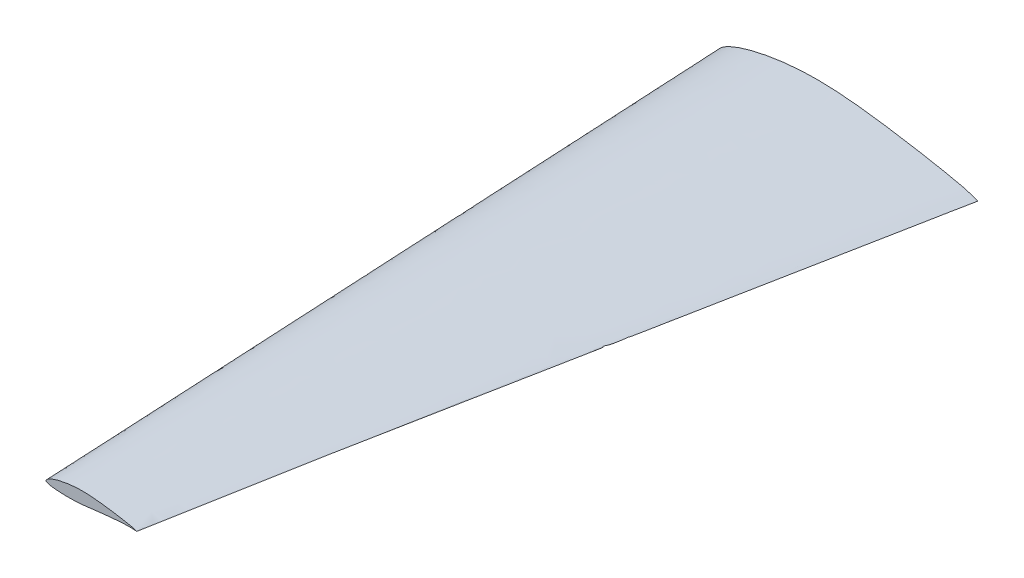
SolidWorks part; units mm, degrees
ref_plane "Front Plane" through (0, 0, 0) normal (0, 0, 1) x (1, 0, 0)
ref_plane "Top Plane" through (0, 0, 0) normal (0, 1, 0) x (1, 0, 0)
ref_plane "Right Plane" through (0, 0, 0) normal (1, 0, 0) x (0, 0, -1)
curve "Curve1"
  spline degree 3 poles (0.9921, 0.0008, 0) (1.0019, -0.0008, 0) (0.9929, 0.0016, 0) (0.9861, 0.0043, 0) (0.9706, 0.0096, 0) (0.9519, 0.0152, 0) (0.9278, 0.021, 0) (0.8992, 0.0273, 0) (0.8662, 0.0341, 0) (0.8293, 0.0413, 0) (0.789, 0.0488, 0) (0.746, 0.0564, 0) (0.7007, 0.0641, 0) (0.6538, 0.0714, 0) (0.6058, 0.0784, 0) (0.5573, 0.0846, 0) (0.5088, 0.0898, 0) (0.4609, 0.0938, 0) (0.4138, 0.0961, 0) (0.3679, 0.0966, 0) (0.3232, 0.0952, 0) (0.2801, 0.092, 0) (0.2388, 0.0874, 0) (0.1997, 0.0815, 0) (0.1631, 0.0746, 0) (0.1296, 0.0669, 0) (0.0993, 0.0585, 0) (0.0726, 0.0496, 0) (0.0499, 0.0404, 0) (0.0312, 0.031, 0) (0.0168, 0.0217, 0) (0.0085, 0.0145, 0) (0.0039, 0.009, 0) (0.0018, 0.0058, 0) (0.0004, 0.0024, 0) (0, 0.0003, 0) (0, -0.0012, 0) (0.0006, -0.0026, 0) (0.002, -0.0043, 0) (0.0049, -0.007, 0) (0.0107, -0.0108, 0) (0.0215, -0.0156, 0) (0.0378, -0.0206, 0) (0.0598, -0.0253, 0) (0.0864, -0.0294, 0) (0.1174, -0.033, 0) (0.1523, -0.036, 0) (0.1908, -0.0383, 0) (0.2323, -0.0397, 0) (0.2764, -0.0402, 0) (0.3228, -0.0395, 0) (0.3711, -0.0373, 0) (0.4212, -0.0335, 0) (0.4729, -0.0284, 0) (0.526, -0.0227, 0) (0.5798, -0.0169, 0) (0.6336, -0.0114, 0) (0.6866, -0.0064, 0) (0.7378, -0.0023, 0) (0.7866, 0.0009, 0) (0.832, 0.0031, 0) (0.8733, 0.0042, 0) (0.9096, 0.0045, 0) (0.9406, 0.0038, 0) (0.9645, 0.0029, 0) (0.984, 0.0013, 0) (0.9921, 0.0008, 0) (1.0019, -0.0008, 0) (0.9929, 0.0016, 0) knots -0.016161 -0.007282 -0.001839 0 0.00178 0.006777 0.014308 0.024046 0.036116 0.050547 0.06713 0.085624 0.105767 0.127282 0.149864 0.17323 0.197069 0.221103 0.245052 0.268663 0.291773 0.314299 0.336178 0.357377 0.377792 0.397225 0.415489 0.432417 0.447849 0.461651 0.473687 0.483898 0.492263 0.498797 0.499955 0.502811 0.504371 0.50536 0.505925 0.506503 0.507535 0.509205 0.512345 0.517665 0.526422 0.537425 0.550643 0.565966 0.583206 0.602155 0.622587 0.644255 0.666998 0.690703 0.715307 0.740824 0.767084 0.793717 0.820331 0.846519 0.871863 0.895937 0.918335 0.938667 0.956573 0.971715 0.983839 0.992718 0.998161 1 1.00178 1.006777 1.014308 periodic
sketch "Sketch1" plane through (0, 0, 0) normal (0, 0, 1) x (1, 0, 0)
  line L0 (1122.2059, -30.8288) -> (-1162.7941, -35.0845) construction
  spline S1 degree 3 poles (1104.1363, -28.0222) (1126.6295, -31.7875) (1105.8826, -26.3024) (1090.4575, -20.1288) (1054.9513, -7.9956) (1012.296, 4.6638) (957.0478, 17.8508) (891.7164, 32.0367) (816.2153, 47.3864) (731.9108, 63.6705) (639.9041, 80.612) (541.5101, 97.9168) (438.0076, 115.0958) (330.7593, 131.7488) (221.0675, 147.3336) (110.2357, 161.251) (-0.493, 172.9975) (-110.0556, 181.8587) (-217.6516, 186.9061) (-322.6724, 187.859) (-424.6755, 184.4831) (-523.1626, 176.9995) (-617.5035, 166.1709) (-706.8843, 152.6667) (-790.3524, 136.737) (-867.0563, 118.889) (-936.2082, 99.5088) (-997.0691, 79.0242) (-1049.0447, 57.9028) (-1091.6336, 36.4479) (-1124.4686, 15.1943) (-1143.3869, -1.4067) (-1153.8659, -14.0298) (-1158.6984, -21.3016) (-1161.9612, -29.0988) (-1162.8988, -33.8887) (-1162.7223, -37.2464) (-1161.3764, -40.4052) (-1158.2301, -44.4654) (-1151.5185, -50.6376) (-1138.2079, -59.2164) (-1113.635, -70.0567) (-1076.2399, -81.3981) (-1026.0446, -92.1031) (-965.2298, -101.4019) (-894.4776, -109.4657) (-814.6314, -116.0953) (-726.7099, -121.1028) (-631.8133, -124.2931) (-530.9633, -125.2112) (-425.0342, -123.2363) (-314.6436, -117.9744) (-200.1569, -109.1265) (-81.9663, -97.1903) (39.2548, -83.9633) (162.1641, -70.4688) (285.0306, -57.6215) (406.0083, -46.0046) (523.1884, -36.2734) (634.6311, -28.7415) (738.3789, -23.5277) (832.7109, -20.7776) (915.5317, -20.0924) (986.36, -21.3847) (1040.9806, -23.338) (1085.6437, -26.9173) (1104.1363, -28.0222) (1126.6295, -31.7875) (1105.8826, -26.3024) knots -0.016161 -0.007282 -0.001839 0 0.00178 0.006777 0.014308 0.024046 0.036116 0.050547 0.06713 0.085624 0.105767 0.127282 0.149864 0.17323 0.197069 0.221103 0.245052 0.268663 0.291773 0.314299 0.336178 0.357377 0.377792 0.397225 0.415489 0.432417 0.447849 0.461651 0.473687 0.483898 0.492263 0.498797 0.499955 0.502811 0.504371 0.50536 0.505925 0.506503 0.507535 0.509205 0.512345 0.517665 0.526422 0.537425 0.550643 0.565966 0.583206 0.602155 0.622587 0.644255 0.666998 0.690703 0.715307 0.740824 0.767084 0.793717 0.820331 0.846519 0.871863 0.895937 0.918335 0.938667 0.956573 0.971715 0.983839 0.992718 0.998161 1 1.00178 1.006777 1.014308 only from (1122.2059, -30.8288) to (1122.2059, -30.8288)
  dimension "D1" = 2285
ref_plane "Plane1" through (0, 0, 6200) normal (0, 0, 1) x (1, 0, 0)
ref_plane "Plane3" through (0, -35.0845, 0) normal (0, 1, 0) x (1, 0, 0)
sketch "Sketch4" plane through (0, -35.0845, 0) normal (0, 1, 0) x (1, 0, 0)
  line L1 (1122.2059, 0) -> (-1162.7941, 0) construction
  line L2 (-172.1886, -6200) -> (172.1886, -6200) construction
  line L4 (-1162.7941, 0) -> (-862.7941, -6200)
sketch "Sketch5" plane through (0, 0, 6200) normal (0, 0, 1) x (1, 0, 0)
  line L0 (-62.749, -35.2354) -> (-862.7688, -35.3009) construction
  spline S1 degree 3 poles (-69.0897, -34.3504) (-61.22, -35.5469) (-68.4893, -33.741) (-73.9048, -31.6671) (-86.3598, -27.6181) (-101.3126, -23.4229) (-120.663, -19.1093) (-143.5377, -14.4998) (-169.9677, -9.5373) (-199.4749, -4.2947) (-231.6736, 1.1372) (-266.1033, 6.6624) (-302.3153, 12.1171) (-339.8318, 17.3686) (-378.1955, 22.2345) (-416.9483, 26.5125) (-455.6538, 30.0335) (-493.9373, 32.5536) (-531.5145, 33.7529) (-568.1715, 33.5367) (-603.7528, 31.8256) (-638.0855, 28.6992) (-670.9538, 24.4271) (-702.0769, 19.2472) (-731.124, 13.2516) (-757.8002, 6.6219) (-781.8329, -0.5031) (-802.9662, -7.9701) (-820.9952, -15.6131) (-835.7466, -23.3233) (-847.0949, -30.9123) (-853.6106, -36.8049) (-857.2018, -41.2651) (-858.8503, -43.8282) (-859.9483, -46.5664) (-860.2505, -48.243) (-860.1714, -49.4139) (-859.6851, -50.5093) (-858.5659, -51.9099) (-856.1913, -54.0289) (-851.5011, -56.9533) (-842.8685, -60.6082) (-829.7584, -64.3709) (-812.1844, -67.8447) (-790.9116, -70.7722) (-766.1771, -73.2167) (-738.2762, -75.1133) (-707.5656, -76.4015) (-674.4302, -77.0191) (-639.2289, -76.8125) (-602.2702, -75.5698) (-563.7715, -73.1566) (-523.8621, -69.4706) (-482.6761, -64.6873) (-440.4393, -59.4377) (-397.6147, -54.086) (-354.8016, -48.9603) (-312.6413, -44.2739) (-271.7964, -40.2655) (-232.9425, -37.0546) (-196.7619, -34.6929) (-163.8546, -33.2402) (-134.9538, -32.5684) (-110.2281, -32.6493) (-91.1554, -33.0456) (-75.5494, -34.0614) (-69.0897, -34.3504) (-61.22, -35.5469) (-68.4893, -33.741) knots -0.016161 -0.007282 -0.001839 0 0.00178 0.006777 0.014308 0.024046 0.036116 0.050547 0.06713 0.085624 0.105767 0.127282 0.149864 0.17323 0.197069 0.221103 0.245052 0.268663 0.291773 0.314299 0.336178 0.357377 0.377792 0.397225 0.415489 0.432417 0.447849 0.461651 0.473687 0.483898 0.492263 0.498797 0.499955 0.502811 0.504371 0.50536 0.505925 0.506503 0.507535 0.509205 0.512345 0.517665 0.526422 0.537425 0.550643 0.565966 0.583206 0.602155 0.622587 0.644255 0.666998 0.690703 0.715307 0.740824 0.767084 0.793717 0.820331 0.846519 0.871863 0.895937 0.918335 0.938667 0.956573 0.971715 0.983839 0.992718 0.998161 1 1.00178 1.006777 1.014308 only from (-62.7688, -35.2354) to (-62.7688, -35.2354)
  dimension "D1" = 800
sketch "Sketch6" plane through (0, 0, 6200) normal (0, 0, 1) x (1, 0, 0)
  line L0 (-862.7688, -35.3009) -> (-860.1517, -49.246)
  spline S0 degree 3 poles (-69.0897, -34.3504) (-61.22, -35.5469) (-68.4893, -33.741) (-73.9048, -31.6671) (-86.3598, -27.6181) (-101.3126, -23.4229) (-120.663, -19.1093) (-143.5377, -14.4998) (-169.9677, -9.5373) (-199.4749, -4.2947) (-231.6736, 1.1372) (-266.1033, 6.6624) (-302.3153, 12.1171) (-339.8318, 17.3686) (-378.1955, 22.2345) (-416.9483, 26.5125) (-455.6538, 30.0335) (-493.9373, 32.5536) (-531.5145, 33.7529) (-568.1715, 33.5367) (-603.7528, 31.8256) (-638.0855, 28.6992) (-670.9538, 24.4271) (-702.0769, 19.2472) (-731.124, 13.2516) (-757.8002, 6.6219) (-781.8329, -0.5031) (-802.9662, -7.9701) (-820.9952, -15.6131) (-835.7466, -23.3233) (-847.0949, -30.9123) (-853.6106, -36.8049) (-857.2018, -41.2651) (-858.8503, -43.8282) (-859.9483, -46.5664) (-860.2505, -48.243) (-860.1714, -49.4139) (-859.6851, -50.5093) (-858.5659, -51.9099) (-856.1913, -54.0289) (-851.5011, -56.9533) (-842.8685, -60.6082) (-829.7584, -64.3709) (-812.1844, -67.8447) (-790.9116, -70.7722) (-766.1771, -73.2167) (-738.2762, -75.1133) (-707.5656, -76.4015) (-674.4302, -77.0191) (-639.2289, -76.8125) (-602.2702, -75.5698) (-563.7715, -73.1566) (-523.8621, -69.4706) (-482.6761, -64.6873) (-440.4393, -59.4377) (-397.6147, -54.086) (-354.8016, -48.9603) (-312.6413, -44.2739) (-271.7964, -40.2655) (-232.9425, -37.0546) (-196.7619, -34.6929) (-163.8546, -33.2402) (-134.9538, -32.5684) (-110.2281, -32.6493) (-91.1554, -33.0456) (-75.5494, -34.0614) (-69.0897, -34.3504) (-61.22, -35.5469) (-68.4893, -33.741) knots -0.016161 -0.007282 -0.001839 0 0.00178 0.006777 0.014308 0.024046 0.036116 0.050547 0.06713 0.085624 0.105767 0.127282 0.149864 0.17323 0.197069 0.221103 0.245052 0.268663 0.291773 0.314299 0.336178 0.357377 0.377792 0.397225 0.415489 0.432417 0.447849 0.461651 0.473687 0.483898 0.492263 0.498797 0.499955 0.502811 0.504371 0.50536 0.505925 0.506503 0.507535 0.509205 0.512345 0.517665 0.526422 0.537425 0.550643 0.565966 0.583206 0.602155 0.622587 0.644255 0.666998 0.690703 0.715307 0.740824 0.767084 0.793717 0.820331 0.846519 0.871863 0.895937 0.918335 0.938667 0.956573 0.971715 0.983839 0.992718 0.998161 1 1.00178 1.006777 1.014308 only from (-62.7688, -35.2354) to (-62.7688, -35.2354) construction
ref_axis "Axis2" through (-860.1517, -49.246, 6200) along (-0.0488, 0.0023, -0.9988)
loft "Loft5" add profiles "Sketch1", "Sketch5" connector at (-829.2128, 127.5517, 0) connector at (-729.5824, 13.4038, 6200)
sketch "Sketch7" plane through (0, 0, 0) normal (0, 0, -1) x (-1, 0, 0)
  line L0 (1162.7941, -35.0845) -> (1162.7941, 315.945)
